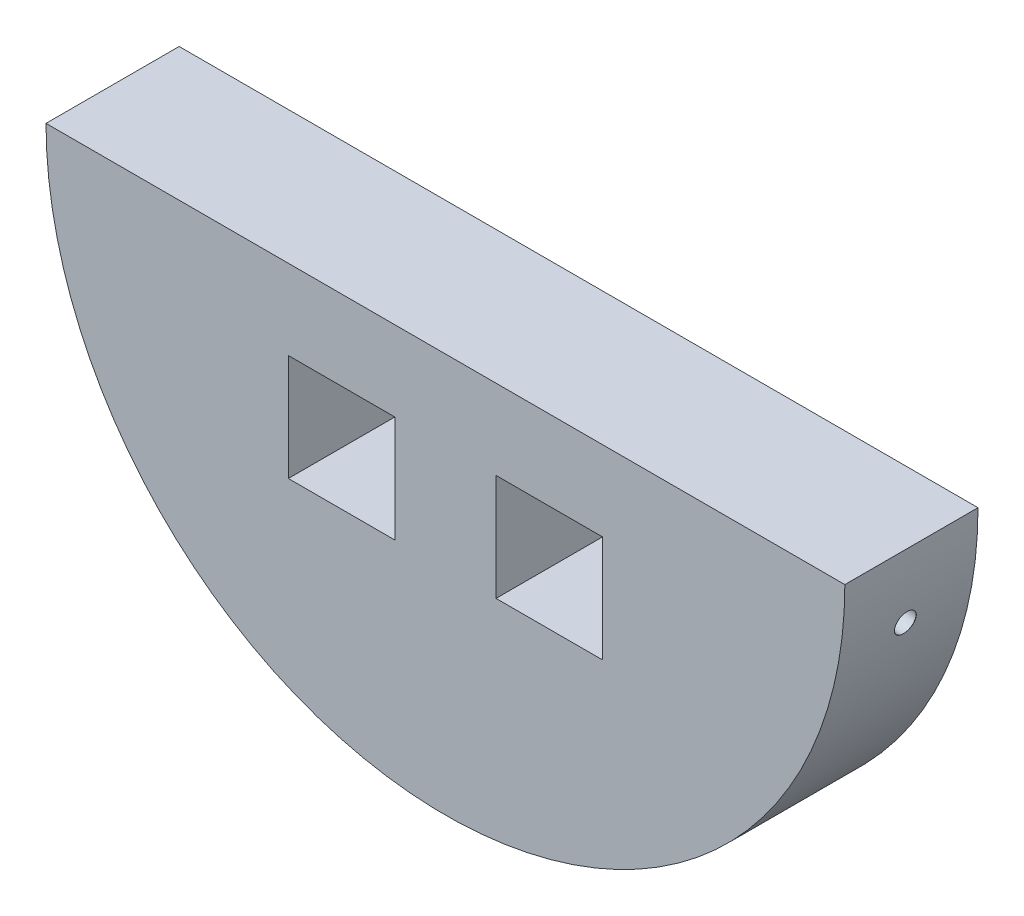
SolidWorks part; units mm, degrees
ref_plane "Front Plane" through (0, 0, 0) normal (0, 0, 1) x (1, 0, 0)
ref_plane "Top Plane" through (0, 0, 0) normal (0, 1, 0) x (1, 0, 0)
ref_plane "Right Plane" through (0, 0, 0) normal (1, 0, 0) x (0, 0, -1)
sketch "Sketch1" plane through (0, 0, 0) normal (0, 0, 1) x (1, 0, 0)
  line L0 (-150, 0) -> (0, 0)
  line L3 (-65.5, -35) -> (-45.5, -35)
  line L4 (-65.5, -35) -> (-65.5, -15)
  line L5 (-65.5, -15) -> (-45.5, -15)
  line L6 (-45.5, -35) -> (-45.5, -15)
  line L7 (-104.5, -35) -> (-84.5, -35)
  line L8 (-104.5, -35) -> (-104.5, -15)
  line L9 (-104.5, -15) -> (-84.5, -15)
  line L10 (-84.5, -35) -> (-84.5, -15)
  arc A1 (-150, 0) -> (0, 0) centre (-75, 0) ccw
  dimension "D1" = 19
  dimension "D7" = 75
  dimension "D2" = 15
  dimension "D3" = 9.5
  dimension "D4" = 20
extrude "Boss-Extrude1" add sketch "Sketch1" along normal blind 25
hole_wizard "Ø4.0mm Dowel Hole2" positions "3DSketch2" profile "Sketch4" hole size "Ø4.0" standard "ANSI Metric"
sketch3d "3DSketch2"
  line L2 (0, 0, 25) -> (0, 0, 0) construction
  line L4 (0, 0, 25) -> (0, 0, 0) construction
  line L5 (0, 0, 12.5) -> (-1.1394, -13.0236, 12.5) construction
  line L8 (-75, 0, 0) -> (-75, 0, 25) construction
  line L9 (0, 0, 0) -> (-150, 0, 0) construction
  line L10 (0, 0, 25) -> (-150, 0, 25) construction
  line L12 (-75, 0, 12.5) -> (-1.1394, -13.0236, 12.5) construction
  line L16 (-75, 0, 12.5) -> (0, 0, 12.5) construction
  point P0 (-1.1394, -13.0236, 12.5)
  point P16 (-1.1394, -13.0236, 12.5)
  point P23 (-1.1394, -13.0236, 12.5)
  point P25 (-1.1394, -13.0236, 12.5)
  dimension "D1" = 10
sketch "Sketch4" plane through (-1.1394, -13.0236, 12.5) normal (0, 0, 1) x (0.1736, 0.9848, 0)
  line L0 (0, 0) -> (0, 17.2017)
  line L1 (0, 17.2017) -> (2, 16)
  line L2 (2, 16) -> (2, 0.025)
  line L3 (2, 0.025) -> (2.025, 0)
  line L5 (2.025, 0) -> (0, 0)
  line L6 (-2, 0.025) -> (-2.025, 0) construction
  line L10 (0, 17.2017) -> (-2, 16) construction
  line L11 (0, -6.35) -> (0, 107.95) construction
  dimension "Hole Dia." = 4
  dimension "Hole Depth" = 16
  dimension "Near C'Sink Dia." = 4.05
  dimension "Near C'Sink Angle" = 90
  dimension "Drill Angle" = 118
pattern_circular "CirPattern1" count 5 over 160 about axis through (-75, 0, 0) along (0, 0, 1) of "Ø4.0mm Dowel Hole2" reverse direction yes
chamfer "Chamfer1" distance 15 angle 30 2 edges at (-94.5, -15, 0) (-55.5, -15, 0) first distance on face at (-94.5, -15, 12.5) first distance on face at (-55.5, -15, 12.5)
